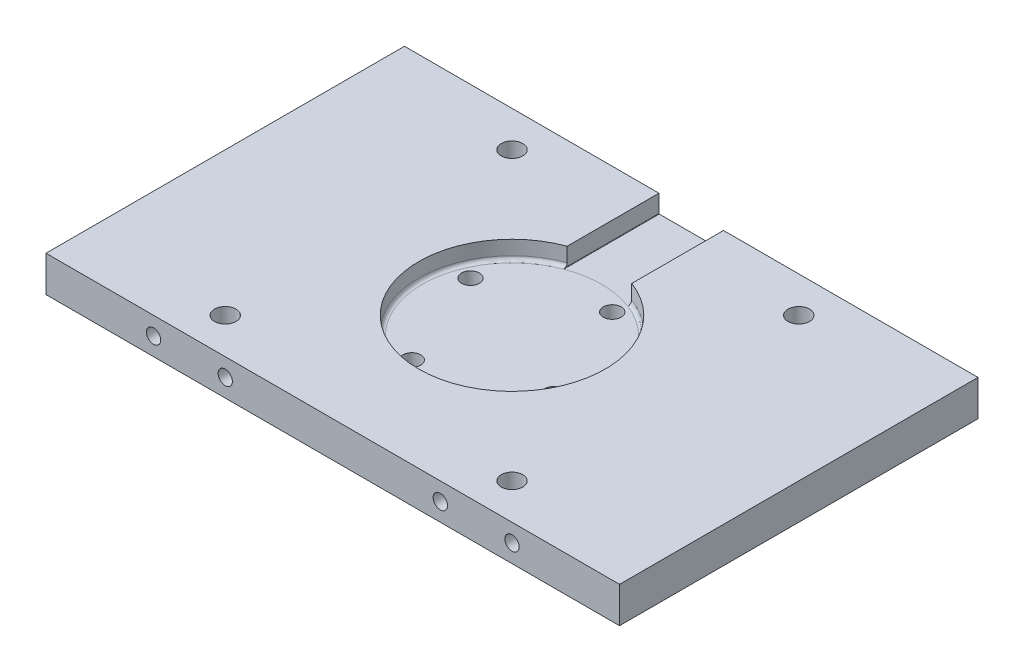
SolidWorks part; units mm, degrees
material "6061-T4 (SS)"
ref_plane "Front Plane" through (0, 0, 0) normal (0, 0, 1) x (1, 0, 0)
ref_plane "Top Plane" through (0, 0, 0) normal (0, 1, 0) x (1, 0, 0)
ref_plane "Right Plane" through (0, 0, 0) normal (1, 0, 0) x (0, 0, -1)
sketch "Sketch1" plane through (0, 0, 0) normal (0, 1, 0) x (1, 0, 0)
  line L1 (80, 50) -> (-80, 50)
  line L2 (80, 50) -> (80, -50)
  line L3 (80, -50) -> (-80, -50)
  line L4 (-80, 50) -> (-80, -50)
  line L5 (80, 50) -> (-80, -50) construction
  line L6 (80, -50) -> (-80, 50) construction
  point P0 (0, 0)
  dimension "D1" = 100
  dimension "D2" = 160
extrude "base" add sketch "Sketch1" along normal blind 10
sketch "Sketch2" plane through (0, 10, 0) normal (0, 1, 0) x (1, 0, 0)
  circle A0 centre (0, 0) radius 26
  dimension "D1" = 52
extrude "load cell cut" cut sketch "Sketch2" against normal blind 5 contours A0
sketch "post positioning points" plane through (0, 10, 0) normal (0, 1, 0) x (1, 0, 0)
  line L0 (-80, 50) -> (-80, -50) construction
  line L1 (-80, -50) -> (80, -50) construction
  line L2 (80, -50) -> (80, 50) construction
  line L3 (80, 50) -> (-80, 50) construction
  point P0 (-40, -40)
  point P5 (20, 40)
  point P6 (-40, 40)
  point P7 (40, 40)
  point P8 (40, -40)
  point P9 (45, -40)
  point P10 (-20, 40)
  dimension "D1" = 40
  dimension "D2" = 10
  dimension "D3" = 40
  dimension "D4" = 10
  dimension "D5" = 85
  dimension "D7" = 60
  dimension "D6" = 60
sketch "Sketch6" plane through (0, 0, -50) normal (0, 0, 1) x (1, 0, 0)
  line L0 (-80, 0) -> (80, 0) construction
  line L1 (9, 10) -> (-9, 10)
  line L2 (9, 10) -> (9, 5)
  line L3 (9, 5) -> (-9, 5)
  line L4 (-9, 10) -> (-9, 5)
  line L5 (9, 10) -> (-9, 5) construction
  line L6 (9, 5) -> (-9, 10) construction
  line L7 (-80, 10) -> (80, 10) construction
  point P0 (0, 7.5)
  point P8 (0, 0)
  dimension "D1" = 18
  dimension "D2" = 5
extrude "cut wire" cut sketch "Sketch6" along normal up to next contours L4 L3 L2 L1
sketch "Sketch7" plane through (0, 0, -50) normal (0, 0, 1) x (1, 0, 0)
  line L1 (5, 10) -> (-5, 10)
  line L2 (5, 10) -> (5, 0)
  line L3 (5, 0) -> (-5, 0)
  line L4 (-5, 10) -> (-5, 0)
  line L5 (5, 10) -> (-5, 0) construction
  line L6 (5, 0) -> (-5, 10) construction
  line L7 (-80, 0) -> (80, 0) construction
  line L8 (-80, 10) -> (80, 10) construction
  point P0 (0, 5)
  point P8 (0, 0)
  dimension "D1" = 10
  dimension "D2" = 10
extrude "cut wire 2" [suppressed] cut sketch "Sketch7" along normal up to next
fillet "Fillet5" [suppressed] radius 10
fillet "Fillet6" radius 0.1 2 edges at (9, 5, -37.1963) (-9, 5, -37.1963)
fillet "Fillet7" [suppressed] radius 5
sketch "Sketch12" plane through (0, 0, 0) normal (0, -1, 0) x (1, 0, 0)
  line L0 (0, 0) -> (80, 0) construction
  line L1 (19.771, 8.1894) -> (-8.1894, 19.771) construction
  line L2 (-8.1894, 19.771) -> (-19.771, -8.1894) construction
  line L3 (-19.771, -8.1894) -> (8.1894, -19.771) construction
  line L4 (8.1894, -19.771) -> (19.771, 8.1894) construction
  line L5 (80, 50) -> (80, -50) construction
  circle A0 centre (0, 0) radius 15.1321 construction
  dimension "D1" = 22.5
  dimension "D2" = 21.4
hole_wizard "Ø5.0mm Dowel Hole1" positions "3DSketch4" profile "Sketch13" hole size "Ø5.0" standard "ANSI Metric" end condition up to next
sketch3d "3DSketch4"
  point P0 (-8.1894, 0, 19.771)
  point P3 (19.771, 0, 8.1894)
  point P6 (8.1894, 0, -19.771)
  point P9 (-19.771, 0, -8.1894)
sketch "Sketch13" plane through (-8.1894, 0, 19.771) normal (1, 0, 0) x (0, 0, -1)
  line L0 (0, 0) -> (0, 5)
  line L1 (0, 5) -> (2.5, 5)
  line L2 (2.5, 5) -> (2.5, 0)
  line L5 (2.5, 0) -> (0, 0)
  line L11 (0, -6.35) -> (0, 107.95) construction
  dimension "Thru Hole Dia." = 5
  dimension "Thru Hole Depth" = 5
fillet "Fillet8" [suppressed] radius 5
sketch "Sketch14" plane through (0, 5, 0) normal (0, 1, 0) x (1, 0, 0)
  circle A0 centre (0, 0) radius 25
  dimension "D1" = 50
split line "Split Line1"
fillet "Fillet9" radius 1 1 edges at (0, 5, 26)
sketch "Sketch15" plane through (0, 0, 0) normal (0, -1, 0) x (-1, 0, 0)
  line L0 (-40, -40) -> (40, -40) construction
  line L1 (40, -40) -> (40, 40) construction
  circle A0 centre (40, -40) radius 3
  circle A1 centre (-40, -40) radius 3
  circle A2 centre (40, 40) radius 3
  circle A3 centre (-40, 40) radius 3
  point P2 (40, 0)
  point P5 (0, -40)
  dimension "D3" = 6
  dimension "D1" = 80
  dimension "D2" = 80
extrude "Cut-Extrude1" cut sketch "Sketch15" against normal up to next
hole_wizard "Ø4.0mm Dowel Hole1" positions "Sketch17" profile "Sketch18" hole size "Ø4.0" standard "ANSI Metric"
sketch "Sketch17" plane through (0, 0, 50) normal (0, 0, 1) x (1, 0, 0)
  point P0 (-50, 5)
  point P3 (-30, 5)
  point P6 (30, 5)
  point P9 (50, 5)
sketch "Sketch18" plane through (-50, 5, 50) normal (1, 0, 0) x (0, -1, 0)
  line L0 (0, 0) -> (0, 11.2017)
  line L1 (0, 11.2017) -> (2, 10)
  line L2 (2, 10) -> (2, 0)
  line L5 (2, 0) -> (0, 0)
  line L10 (0, 11.2017) -> (-2, 10) construction
  line L11 (0, -6.35) -> (0, 107.95) construction
  dimension "Hole Dia." = 4
  dimension "Hole Depth" = 10
  dimension "Drill Angle" = 118
cosmetic thread "Cosmetic Thread1" parameters "D2"=4
cosmetic thread "Cosmetic Thread2" parameters "D2"=5
cosmetic thread "Cosmetic Thread3" parameters "D2"=4
cosmetic thread "Cosmetic Thread4" parameters "D2"=4
cosmetic thread "Cosmetic Thread9" parameters "D2"=5
cosmetic thread "Cosmetic Thread11" parameters "D2"=5
cosmetic thread "Cosmetic Thread13" parameters "D2"=5
mirror "Mirror1" about plane through (0, 0, 0) normal (0, 0, 1) of "Ø4.0mm Dowel Hole1"
cosmetic thread "Cosmetic Thread5" parameters "D2"=5
cosmetic thread "Cosmetic Thread6" parameters "D2"=4
cosmetic thread "Cosmetic Thread7" parameters "D2"=4
cosmetic thread "Cosmetic Thread8" parameters "D2"=4
cosmetic thread "Cosmetic Thread10" parameters "D2"=5
cosmetic thread "Cosmetic Thread12" parameters "D2"=5
cosmetic thread "Cosmetic Thread14" parameters "D2"=5
cosmetic thread "Cosmetic Thread15" parameters "D2"=5
cosmetic thread "Cosmetic Thread16" parameters "D2"=5
cosmetic thread "Cosmetic Thread17" parameters "D2"=5
cosmetic thread "Cosmetic Thread18" parameters "D2"=5
equation "\"D2@post positioning points\"=10"
equation "\"D3@post positioning points\"=\"D1@post positioning points\""
equation "\"D4@post positioning points\"=\"D2@post positioning points\""
equation "\"D1@base\"=10"
equation "\"D1@load cell cut\"=5"
equation "\"D2@Sketch6\"=5"
